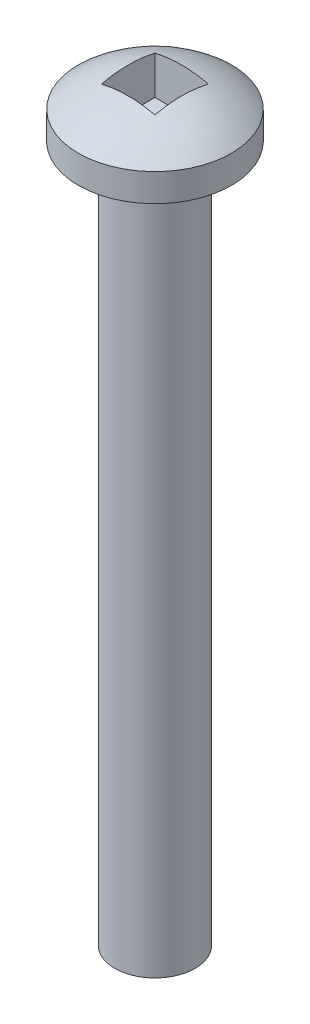
SolidWorks part; units mm, degrees
material "Cast Alloy Steel"
ref_plane "Front Plane" through (0, 0, 0) normal (0, 0, 1) x (1, 0, 0)
ref_plane "Top Plane" through (0, 0, 0) normal (0, 1, 0) x (1, 0, 0)
ref_plane "Right Plane" through (0, 0, 0) normal (1, 0, 0) x (0, 0, -1)
sketch "Sketch1" plane through (0, 0, 0) normal (0, 1, 0) x (1, 0, 0)
  circle A0 centre (0, 0) radius 1.8288
  dimension "D1" = 3.6576
extrude "Boss-Extrude1" add sketch "Sketch1" against normal blind 31.75
sketch "Sketch2" plane through (0, 0, 0) normal (0, 1, 0) x (1, 0, 0)
  circle A0 centre (0, 0) radius 3.4925
  dimension "D1" = 6.985
extrude "Boss-Extrude2" add sketch "Sketch2" along normal blind 1.27
dome "Dome1" faces to dome 1 distance 1.27 reverse direction no elliptical dome no face at (0, 1.27, 3.4925) parameters "D1"=1.27
ref_plane "Plane1" through (0, 2.54, 0) normal (0, 1, 0) x (1, 0, 0)
sketch "Sketch3" plane through (0, 2.54, 0) normal (0, 1, 0) x (1, 0, 0)
  line L1 (-1.2192, -1.2192) -> (1.2192, -1.2192)
  line L2 (-1.2192, -1.2192) -> (-1.2192, 1.2192)
  line L3 (-1.2192, 1.2192) -> (1.2192, 1.2192)
  line L4 (1.2192, -1.2192) -> (1.2192, 1.2192)
  line L5 (-1.2192, -1.2192) -> (1.2192, 1.2192) construction
  line L6 (-1.2192, 1.2192) -> (1.2192, -1.2192) construction
  point P0 (0, 0)
  dimension "D1" = 2.4384
extrude "Cut-Extrude1" cut sketch "Sketch3" against normal blind 2.032
